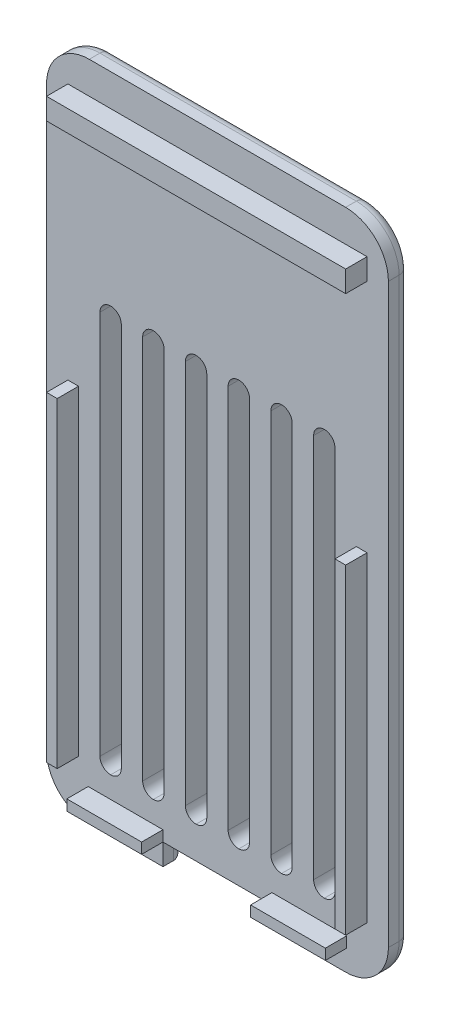
SolidWorks part; units mm, degrees
ref_plane "Front Plane" through (0, 0, 0) normal (0, 0, 1) x (1, 0, 0)
ref_plane "Top Plane" through (0, 0, 0) normal (0, 1, 0) x (1, 0, 0)
ref_plane "Right Plane" through (0, 0, 0) normal (1, 0, 0) x (0, 0, -1)
sketch "Sketch1" plane through (0, 0, 0) normal (0, 0, 1) x (1, 0, 0)
  line L7 (-16, 31) -> (16, 31)
  line L8 (-16, 31) -> (-16, -31)
  line L9 (-16, -31) -> (16, -31)
  line L10 (16, 31) -> (16, -31)
  line L11 (-16, 31) -> (16, -31) construction
  line L12 (-16, -31) -> (16, 31) construction
  point P0 (0, 0)
  point P1 (0, 0)
  point P6 (0, 0)
  dimension "D1" = 32
  dimension "D2" = 62
extrude "Boss-Extrude4" add sketch "Sketch1" along normal blind 2
sketch "Sketch6" plane through (0, 0, 2) normal (0, 0, 1) x (1, 0, 0)
  line L0 (-16, 31) -> (-16, -31) construction
  line L2 (14, 28) -> (-14, 28)
  line L4 (-14, 28) -> (-14, 26)
  line L9 (-14, 26) -> (14, 26)
  line L10 (14, 26) -> (14, 28)
  line L14 (16, -31) -> (16, 31) construction
  line L15 (16, 31) -> (-16, 31) construction
  line L16 (0, 0) -> (0, -31) construction
  line L18 (-16, -31) -> (16, -31) construction
  line L19 (0, -31) -> (-5.1, -31) construction
  line L30 (-12.1, -29) -> (-12.1, -28)
  line L31 (-12.1, -28) -> (-5.1, -28)
  line L32 (-5.1, -29) -> (-12.1, -29)
  line L33 (-5.1, -28) -> (-5.1, -29)
  line L34 (-13, -26) -> (-13, 4)
  line L35 (-13, 4) -> (-14, 4)
  line L36 (-14, 4) -> (-14, -26)
  line L37 (-14, -26) -> (-13, -26)
  line L38 (14, 4) -> (14, -26)
  line L39 (13, 4) -> (14, 4)
  line L40 (13, -26) -> (13, 4)
  line L41 (14, -26) -> (13, -26)
  line L42 (12.1, -29) -> (12.1, -28)
  line L43 (5.1, -29) -> (12.1, -29)
  line L44 (5.1, -28) -> (5.1, -29)
  line L45 (12.1, -28) -> (5.1, -28)
  point P8 (0, 28)
  point P23 (-0.5124, -31)
  point P25 (-13.5, -26)
  dimension "D1" = 2
  dimension "D2" = 2
  dimension "D3" = 2
  dimension "D4" = 3
  dimension "D5" = 1
  dimension "D6" = 7
  dimension "D7" = 1
  dimension "D8" = 30
  dimension "D9" = 2
  dimension "D10" = 2
  dimension "D11" = 5
extrude "Boss-Extrude6" add sketch "Sketch6" along normal blind 2 contours L10 L2 L4 L9 | L34 L35 L36 L37 | L40 L39 L38 L41 | L42 L45 L44 L43 | L31 L33 L32 L30
sketch "Sketch7" plane through (0, 0, 0) normal (0, 0, -1) x (-1, 0, 0)
  line L0 (16, 31) -> (16, -31) construction
  line L1 (13.0003, 23) -> (2.9997, 23)
  line L3 (12.2919, 21) -> (3.7081, 21)
  line L4 (-16, 31) -> (16, 31) construction
  line L6 (12.2919, 21) -> (12.2919, 25)
  line L7 (12.2919, 25) -> (3.7081, 25)
  line L8 (3.7081, 21) -> (3.7081, 25)
  line L9 (12.2919, 21) -> (3.7081, 25) construction
  line L10 (12.2919, 25) -> (3.7081, 21) construction
  line L15 (-3.0909, 19.875) -> (-12.9091, 19.875)
  line L16 (-3.0909, 19.875) -> (-3.0909, 26.125)
  line L17 (-3.0909, 26.125) -> (-12.9091, 26.125)
  line L18 (-12.9091, 19.875) -> (-12.9091, 26.125)
  line L19 (-3.0909, 19.875) -> (-12.9091, 26.125) construction
  line L20 (-3.0909, 26.125) -> (-12.9091, 19.875) construction
  line L69 (7.4496, 19.9021) -> (7.4496, 26.125)
  line L70 (9.0672, 19.9021) -> (7.4496, 19.9021)
  line L71 (9.0672, 20.6157) -> (9.0672, 19.9021)
  line L72 (8.2416, 20.6157) -> (9.0672, 20.6157)
  line L73 (8.2416, 26.125) -> (8.2416, 20.6157)
  line L74 (7.4496, 26.125) -> (8.2416, 26.125)
  line L75 (-7.1469, 25.3765) -> (-10.1083, 25.3765)
  line L76 (-6.7522, 21.7787) -> (-5.9938, 21.7787)
  line L77 (-5.9689, 26.0315) -> (-5.9689, 25.4711)
  line L78 (-10.1083, 26.0315) -> (-5.9689, 26.0315)
  line L79 (-10.1083, 25.3765) -> (-10.1083, 26.0315)
  circle A2 centre (8, 23) radius 6
  circle A3 centre (8, 23) radius 5.0003
  circle A4 centre (-8, 23) radius 5.0003
  circle A5 centre (-8, 23) radius 6
  spline S0 degree 3 poles (-9.9278, 21.6068) (-9.9282, 21.7256) (-9.915, 21.904) (-9.8701, 22.1385) (-9.8224, 22.3131) (-9.7623, 22.4865) (-9.6903, 22.6593) (-9.6023, 22.8296) (-9.4694, 23.0543) (-9.2856, 23.3238) (-9.0522, 23.6327) (-8.8023, 23.9199) (-8.5798, 24.144) (-8.3912, 24.3178) (-8.2419, 24.4541) (-8.0819, 24.5945) (-7.9135, 24.7413) (-7.7345, 24.8918) (-7.4799, 25.1062) (-7.2831, 25.2685) (-7.1469, 25.3765) knots 0 0 0 0 0.073605 0.110554 0.14789 0.185738 0.224265 0.263861 0.304471 0.386062 0.465953 0.544399 0.621927 0.661628 0.703352 0.747296 0.793638 0.84185 0.892269 1 1 1 1
  spline S1 degree 3 poles (-8, 19.765) (-8.141, 19.7635) (-8.347, 19.7805) (-8.6123, 19.8291) (-8.7937, 19.8856) (-8.9656, 19.9531) (-9.1253, 20.0382) (-9.2734, 20.1386) (-9.4092, 20.2532) (-9.5318, 20.3814) (-9.6374, 20.5228) (-9.7287, 20.6745) (-9.8005, 20.8394) (-9.8577, 21.015) (-9.9145, 21.2704) (-9.926, 21.4708) (-9.9278, 21.6068) knots 0 0 0 0 0.139977 0.205129 0.267662 0.328584 0.388398 0.44723 0.506092 0.564764 0.623116 0.681221 0.740344 0.801549 0.864528 1 1 1 1
  spline S2 degree 3 poles (-5.9938, 21.7787) (-5.9975, 21.626) (-6.023, 21.4036) (-6.0878, 21.1191) (-6.1545, 20.9256) (-6.2353, 20.7449) (-6.3327, 20.5778) (-6.4481, 20.4256) (-6.5778, 20.2874) (-6.7195, 20.1634) (-6.874, 20.0582) (-7.0364, 19.9654) (-7.2103, 19.8928) (-7.3936, 19.8349) (-7.6563, 19.7791) (-7.8614, 19.7664) (-8, 19.765) knots 0 0 0 0 0.143256 0.209727 0.273584 0.335171 0.395275 0.454839 0.514133 0.57299 0.631273 0.689392 0.748256 0.807927 0.869702 1 1 1 1
  spline S3 degree 3 poles (-8.0087, 20.4362) (-7.9164, 20.438) (-7.7803, 20.4453) (-7.6076, 20.4847) (-7.4895, 20.5249) (-7.3789, 20.5754) (-7.2781, 20.6402) (-7.1833, 20.7135) (-7.0988, 20.8001) (-7.0237, 20.8961) (-6.9551, 20.9986) (-6.8985, 21.1103) (-6.8493, 21.2287) (-6.8111, 21.3556) (-6.7703, 21.5384) (-6.7568, 21.6816) (-6.7522, 21.7787) knots 0 0 0 0 0.134196 0.196563 0.256347 0.314798 0.372428 0.429881 0.488208 0.547353 0.606467 0.666785 0.728615 0.792224 0.858835 1 1 1 1
  spline S4 degree 3 poles (-9.1532, 21.6417) (-9.1551, 21.5529) (-9.1445, 21.4231) (-9.117, 21.2562) (-9.0862, 21.142) (-9.0498, 21.0341) (-9.0021, 20.9348) (-8.9467, 20.8426) (-8.8834, 20.7574) (-8.8101, 20.6808) (-8.7249, 20.6159) (-8.6315, 20.559) (-8.5263, 20.5147) (-8.4118, 20.4781) (-8.2386, 20.4448) (-8.1024, 20.4361) (-8.0087, 20.4362) knots 0 0 0 0 0.139728 0.204785 0.266341 0.325916 0.383845 0.439595 0.495192 0.5507 0.606173 0.663382 0.722557 0.78565 0.852353 1 1 1 1
  spline S5 degree 3 poles (-5.9689, 25.4711) (-6.142, 25.3322) (-6.3931, 25.128) (-6.7172, 24.8609) (-6.9384, 24.6757) (-7.1452, 24.5002) (-7.337, 24.3341) (-7.515, 24.1793) (-7.7299, 23.9863) (-7.978, 23.7492) (-8.254, 23.4592) (-8.5019, 23.1594) (-8.6927, 22.9063) (-8.8272, 22.7005) (-8.9149, 22.548) (-8.9873, 22.3949) (-9.0472, 22.243) (-9.0951, 22.0922) (-9.1401, 21.8931) (-9.1536, 21.7419) (-9.1532, 21.6417) knots 0 0 0 0 0.130041 0.189653 0.246119 0.299099 0.348596 0.394796 0.43734 0.517856 0.595805 0.671799 0.745699 0.781391 0.815816 0.848676 0.880566 0.911417 0.941336 1 1 1 1
  point P5 (-0.232, 31)
  point P10 (8, 23)
  point P13 (8, 23)
  point P20 (-8, 23)
  point P33 (-8, 23)
  point P149 (8, 23)
  dimension "D1" = 8
  dimension "D2" = 8
extrude "Cut-Extrude3" cut sketch "Sketch7" against normal blind 1.5 contours A2 | L69 L74 L73 L72 L71 L70 | A3 | A5 | L75 L79 L78 L77 S5 S4 S3 L76 S2 S1 S0 | A4
sketch "Sketch8" plane through (0, 0, 0) normal (0, 0, -1) x (-1, 0, 0)
  line L0 (0, -31) -> (0, -26)
  line L1 (16, -31) -> (-16, -31) construction
  line L2 (-8, 17) -> (8, 17)
  line L3 (0, 17) -> (0, 12)
  line L4 (16, 0) -> (11, 0) construction
  line L5 (16, 31) -> (16, -31) construction
  line L6 (-16, 0) -> (-12, 0) construction
  line L7 (-16, -31) -> (-16, 31) construction
  line L8 (0, 12) -> (12, 12) construction
  line L9 (0, -26) -> (12, -26) construction
  line L10 (11, 0) -> (10, 0)
  line L15 (11, -26) -> (11, 12)
  line L16 (11, 12) -> (9, 12)
  line L17 (9, 12) -> (9, -26)
  line L18 (9, -26) -> (11, -26)
  line L19 (7, -26) -> (9, -26)
  line L20 (9, -26) -> (9, 12)
  line L21 (9, 12) -> (7, 12)
  line L22 (7, 12) -> (7, -26)
  line L23 (5, -26) -> (7, -26)
  line L24 (7, -26) -> (7, 12)
  line L25 (7, 12) -> (5, 12)
  line L26 (5, 12) -> (5, -26)
  line L27 (3, -26) -> (5, -26)
  line L28 (5, -26) -> (5, 12)
  line L29 (5, 12) -> (3, 12)
  line L30 (3, 12) -> (3, -26)
  line L31 (1, -26) -> (3, -26)
  line L32 (3, -26) -> (3, 12)
  line L33 (3, 12) -> (1, 12)
  line L34 (1, 12) -> (1, -26)
  line L35 (-1, -26) -> (1, -26)
  line L36 (1, -26) -> (1, 12)
  line L37 (1, 12) -> (-1, 12)
  line L38 (-1, 12) -> (-1, -26)
  line L39 (-3, -26) -> (-1, -26)
  line L40 (-1, -26) -> (-1, 12)
  line L41 (-1, 12) -> (-3, 12)
  line L42 (-3, 12) -> (-3, -26)
  line L43 (-5, -26) -> (-3, -26)
  line L44 (-3, -26) -> (-3, 12)
  line L45 (-3, 12) -> (-5, 12)
  line L46 (-5, 12) -> (-5, -26)
  line L47 (-7, -26) -> (-5, -26)
  line L48 (-5, -26) -> (-5, 12)
  line L49 (-5, 12) -> (-7, 12)
  line L50 (-7, 12) -> (-7, -26)
  line L51 (-9, -26) -> (-7, -26)
  line L52 (-7, -26) -> (-7, 12)
  line L53 (-7, 12) -> (-9, 12)
  line L54 (-9, 12) -> (-9, -26)
  line L55 (-11, -26) -> (-9, -26)
  line L56 (-9, -26) -> (-9, 12)
  line L57 (-9, 12) -> (-11, 12)
  line L58 (-11, 12) -> (-11, -26)
  circle A0 centre (-8, 23) radius 6 construction
  circle A1 centre (8, 23) radius 6 construction
  dimension "D1" = 5
  dimension "D2" = 11
  dimension "D3" = 5
  dimension "D4" = 5
extrude "Cut-Extrude5" cut sketch "Sketch8" against normal blind 2 contours L25 L26 L23 L22 | L33 L34 L31 L30 | L41 L42 L39 L38 | L49 L50 L47 L46 | L57 L58 L55 L54 | L17 L18 L15 L16 region at (-6, -7, 0) region at (-2, -7, 0) region at (2, -7, 0) region at (6, -7, 0) region at (10, -7, 0)
sketch "Sketch26" plane through (0, -31, 0) normal (0, -1, 0) x (1, 0, 0)
  line L0 (-5.1, 0) -> (5.1, 0)
  line L1 (-16, 0) -> (16, 0) construction
  line L2 (5.1, 0) -> (5.1, 2)
  line L3 (5.1, 2) -> (-5.1, 2)
  line L4 (-5.1, 2) -> (-5.1, 0)
  point P5 (0, 0)
extrude "Cut-Extrude11" cut sketch "Sketch26" against normal blind 2
fillet "Fillet3" radius 1 24 edges at (-9, 12, 1) (-5, 12, 1) (-1, 12, 1) (3, 12, 1) (7, 12, 1) (11, 12, 1) (9, 12, 1) (5, 12, 1) (1, 12, 1) (-3, 12, 1) (-7, 12, 1) (-11, 12, 1) (-5, -26, 1) (-1, -26, 1) (3, -26, 1) (7, -26, 1) (11, -26, 1) (9, -26, 1) (5, -26, 1) (1, -26, 1) (-3, -26, 1) (-7, -26, 1) (-9, -26, 1) (-11, -26, 1)
fillet "Fillet5" radius 4 4 edges at (-16, 31, 1) (-16, -31, 1) (16, -31, 1) (16, 31, 1)
fillet "Fillet6" radius 1 12 edges at (8.55, -31, 0) (14.8284, -29.8284, 0) (-8.55, -31, 0) (-14.8284, -29.8284, 0) (-16, 0, 0) (-14.8284, 29.8284, 0) (0, 31, 0) (14.8284, 29.8284, 0) (-5.1, -30, 0) (0, -29, 0) (5.1, -30, 0) (16, 0, 0)
